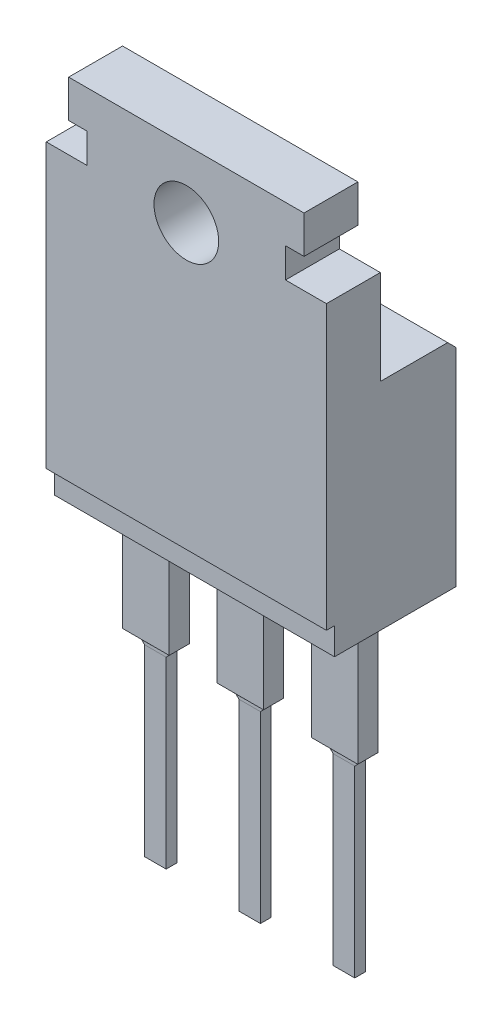
SolidWorks part; units mm, degrees
ref_plane "Front Plane" through (0, 0, 0) normal (0, 0, 1) x (1, 0, 0)
ref_plane "Top Plane" through (0, 0, 0) normal (0, 1, 0) x (1, 0, 0)
ref_plane "Right Plane" through (0, 0, 0) normal (1, 0, 0) x (0, 0, -1)
sketch "Sketch1" plane through (0, 0, 0) normal (1, 0, 0) x (0, 0, -1)
  line L0 (-2550, 14000) -> (-2550, 1000)
  line L1 (-2250, 0) -> (2250, 0)
  line L2 (2250, 0) -> (2250, 7700)
  line L3 (1950, 8000) -> (-2550, 8000)
  line L4 (-2550, 14000) -> (-550, 14000)
  line L5 (-550, 14000) -> (-550, 8000)
  line L6 (-2550, 12604.5895) -> (-550, 12604.5895)
  line L7 (-2250, 0) -> (-2250, 1000)
  line L8 (-2250, 1000) -> (-2550, 1000)
  line L9 (-2550, 11502.1484) -> (-550, 11502.1484)
  line L10 (311.8764, 0) -> (311.8764, -12000)
  line L11 (311.8764, -12000) -> (-88.1236, -12000)
  line L12 (-88.1236, -12000) -> (-88.1236, -5187.2823)
  line L13 (-88.1236, -5187.2823) -> (-550, -4725.4059)
  line L14 (-550, -4725.4059) -> (-550, 0)
  line L15 (2250, 7700) -> (1950, 8000)
  point P4 (2250, 8000)
sketch "Sketch2" plane through (0, 0, 0) normal (0, 0, 1) x (1, 0, 0)
  line L0 (-400, -12000) -> (400, -12000)
  line L1 (-5200, 0) -> (5200, 0)
  line L2 (-3900, -12000) -> (-3100, -12000)
  line L3 (400, -12000) -> (400, -5187.2823)
  line L4 (400, -5187.2823) -> (862.4992, -4724.7831)
  line L5 (862.4992, -4724.7831) -> (862.4992, 0)
  line L6 (-3100, -12000) -> (-3100, -5187.2823)
  line L7 (-400, -12000) -> (-400, -5187.2823)
  line L8 (-400, -5187.2823) -> (-862.4992, -4724.7831)
  line L9 (-862.4992, -4724.7831) -> (-862.4992, 0)
  line L10 (4362.4992, -4724.7831) -> (2637.5008, -4724.7831)
  line L11 (3100, -12000) -> (3900, -12000)
  line L12 (3900, -12000) -> (3900, -5187.2823)
  line L13 (3900, -5187.2823) -> (4362.4992, -4724.7831)
  line L14 (4362.4992, -4724.7831) -> (4362.4992, 0)
  line L15 (3100, -12000) -> (3100, -5187.2823)
  line L16 (3100, -5187.2823) -> (2637.5008, -4724.7831)
  line L17 (2637.5008, -4724.7831) -> (2637.5008, 0)
  line L18 (-3100, -5187.2823) -> (-2637.5008, -4724.7831)
  line L19 (-2637.5008, -4724.7831) -> (-2637.5008, 0)
  line L20 (-3900, -12000) -> (-3900, -5187.2823)
  line L21 (-3900, -5187.2823) -> (-4362.4992, -4724.7831)
  line L22 (-4362.4992, -4724.7831) -> (-4362.4992, 0)
  line L24 (5200, 8016.2982) -> (5200, 0)
  line L25 (-5200, 8016.2982) -> (-5200, 0)
  line L26 (-3676.8797, 11502.3136) -> (-5200, 11502.3136)
  line L27 (-862.4992, -4267.2823) -> (862.4992, -4267.2823)
  line L28 (-5200, 11502.3136) -> (-5200, 8016.2982)
  line L29 (5200, 11502.3136) -> (5200, 8016.2982)
  line L30 (-3676.8797, 12604.5641) -> (-4362.4992, 12604.5641)
  line L31 (4367.5008, 14000) -> (4367.5008, 12604.5641)
  line L32 (-3676.8797, 12604.5641) -> (-3676.8797, 11502.3136)
  line L33 (-4362.4992, 12604.5641) -> (-4362.4992, 14000)
  line L34 (-4362.4992, 14000) -> (4367.5008, 14000)
  line L35 (-3900, -5187.2823) -> (-3100, -5187.2823)
  line L36 (-2637.5008, -4267.2823) -> (-4362.4992, -4267.2823)
  line L37 (4367.5008, 12604.5641) -> (3677.5008, 12604.5641)
  line L38 (3677.5008, 12604.5641) -> (3677.5008, 11502.3136)
  line L39 (3677.5008, 11502.3136) -> (5200, 11502.3136)
  line L40 (-400, -5187.2823) -> (400, -5187.2823)
  line L41 (2637.5008, -4267.2823) -> (4362.4992, -4267.2823)
  line L42 (3100, -5187.2823) -> (3900, -5187.2823)
  line L43 (862.4992, -4724.7831) -> (-862.4992, -4724.7831)
  line L44 (-2637.5008, -4724.7831) -> (-4362.4992, -4724.7831)
  circle A0 centre (0, 11502.3136) radius 1200
extrude "Boss-Extrude1" add sketch "Sketch2" along normal mid plane 400 contours L42 L15 L11 L12 | L40 L7 L0 L3 | L35 L20 L2 L6 region at (0, -8593.6411, 0) region at (-3500, -8593.6411, 0) region at (3500, -8593.6411, 0)
sketch "Sketch4" plane through (0, 0, 0) normal (1, 0, 0) x (0, 0, -1)
  line L0 (-2550, 8000) -> (1950, 8000)
  line L1 (1950, 8000) -> (2250, 7700)
  line L2 (2250, 7700) -> (2250, 0)
  line L3 (2250, 0) -> (-2250, 0)
  line L4 (-2250, 0) -> (-2250, 1000)
  line L5 (-2250, 1000) -> (-2550, 1000)
  line L6 (-2550, 1000) -> (-2550, 8000)
extrude "Boss-Extrude9" add sketch "Sketch4" along normal mid plane 10400 separate body
sketch "Sketch5" plane through (0, 0, 0) normal (1, 0, 0) x (0, 0, -1)
  line L0 (-2550, 8000) -> (-2550, 11502.1484)
  line L1 (-2550, 11502.1484) -> (-550, 11502.1484)
  line L2 (-550, 11502.1484) -> (-550, 8000)
  line L3 (-550, 8000) -> (-2550, 8000)
sketch "Sketch6" plane through (0, 0, 0) normal (1, 0, 0) x (0, 0, -1)
  line L0 (-550, 12604.5895) -> (-550, 14000)
  line L1 (-550, 14000) -> (-2550, 14000)
  line L2 (-2550, 14000) -> (-2550, 12604.5895)
  line L3 (-2550, 12604.5895) -> (-550, 12604.5895)
sketch "Sketch7" plane through (0, 0, 0) normal (1, 0, 0) x (0, 0, -1)
  line L0 (-550, 11502.1484) -> (-550, 12604.5895)
  line L1 (-550, 12604.5895) -> (-2550, 12604.5895)
  line L2 (-2550, 12604.5895) -> (-2550, 11502.1484)
  line L3 (-2550, 11502.1484) -> (-550, 11502.1484)
extrude "Boss-Extrude10" add sketch "Sketch5" along normal mid plane 10400
extrude "Boss-Extrude11" add sketch "Sketch7" along normal mid plane 7361
extrude "Boss-Extrude12" add sketch "Sketch6" along normal mid plane 8736
extrude "Cut-Extrude1" cut sketch "Sketch2<14>" against normal mid plane 8736 contours A0
sketch "Sketch2<14>" plane through (0, 0, 0) normal (0, 0, 1) x (1, 0, 0) same geometry as "Sketch2"
sketch "Sketch8" plane through (0, 0, 0) normal (0, 0, 1) x (1, 0, 0)
  line L0 (-4362.4992, 0) -> (-4362.4992, -4724.7831)
  line L1 (-4362.4992, -4724.7831) -> (-2637.5008, -4724.7831)
  line L2 (-2637.5008, -4724.7831) -> (-2637.5008, 0)
  line L3 (-2637.5008, 0) -> (-4362.4992, 0)
  line L4 (-862.4992, 0) -> (-862.4992, -4724.7831)
  line L5 (-862.4992, -4724.7831) -> (862.4992, -4724.7831)
  line L6 (862.4992, -4724.7831) -> (862.4992, 0)
  line L7 (862.4992, 0) -> (-862.4992, 0)
  line L8 (2637.5008, 0) -> (4362.4992, 0)
  line L9 (4362.4992, 0) -> (4362.4992, -4724.7831)
  line L10 (4362.4992, -4724.7831) -> (2637.5008, -4724.7831)
  line L11 (2637.5008, -4724.7831) -> (2637.5008, 0)
extrude "Boss-Extrude14" add sketch "Sketch8" along normal blind 548 and the other way blind 197
extrude "Boss-Extrude15" add sketch "Sketch2<16>" against normal blind 200 contours L18 L44 L21 L35 | L4 L43 L8 L40 | L16 L42 L13 L10 region at (0, -4927.7943, 0) region at (-3500, -4927.7943, 0) region at (3500, -4927.7943, 0)
sketch "Sketch2<16>" plane through (0, 0, 0) normal (0, 0, 1) x (1, 0, 0) same geometry as "Sketch2"
extrude "Boss-Extrude16" add sketch "Sketch2<17>" along normal blind 619 draft 40 separate body contours L18 L44 L21 L35 | L4 L43 L8 L40 | L16 L42 L13 L10 | L44 L19 L36 L22 | L43 L5 L27 L9 | L41 L17 L10 L14 region at (0, -4927.7943, 0) region at (0, -4496.0327, 0) region at (-3500, -4496.0327, 0) region at (3500, -4496.0327, 0) region at (-3500, -4927.7943, 0) region at (3500, -4927.7943, 0)
sketch "Sketch2<17>" plane through (0, 0, 0) normal (0, 0, 1) x (1, 0, 0) same geometry as "Sketch2"
extrude "Boss-Extrude17" add sketch "Sketch2<18>" along normal blind 200 separate body contours L18 L44 L21 L35 | L4 L43 L8 L40 | L16 L42 L13 L10 region at (0, -4927.7943, 0) region at (-3500, -4927.7943, 0) region at (3500, -4927.7943, 0)
sketch "Sketch2<18>" plane through (0, 0, 0) normal (0, 0, 1) x (1, 0, 0) same geometry as "Sketch2"
